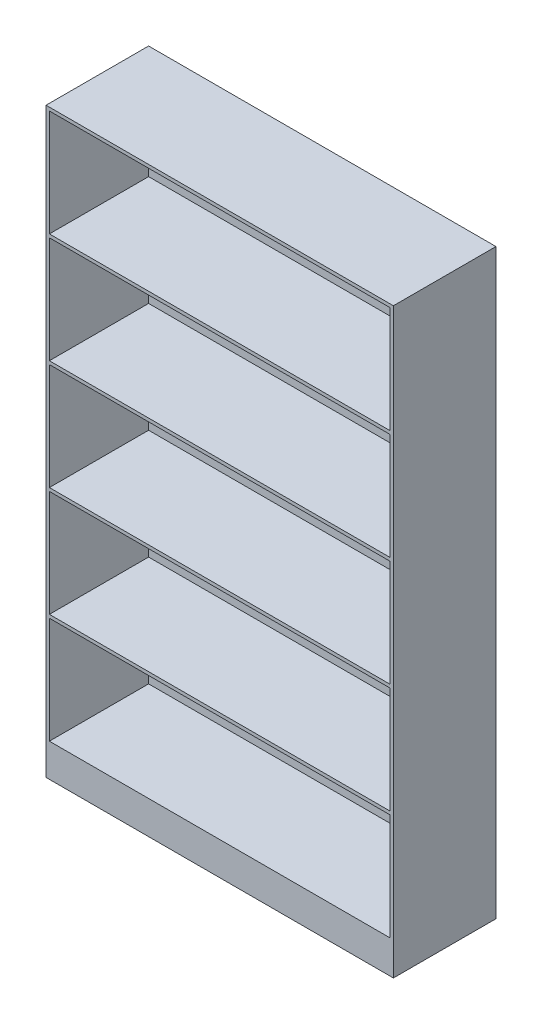
SolidWorks part; units mm, degrees
ref_plane "Alzado" through (0, 0, 0) normal (0, 0, 1) x (1, 0, 0)
ref_plane "Planta" through (0, 0, 0) normal (0, 1, 0) x (1, 0, 0)
ref_plane "Vista lateral" through (0, 0, 0) normal (1, 0, 0) x (0, 0, -1)
sketch "Croquis1" plane through (0, 0, 0) normal (0, 0, 1) x (1, 0, 0)
  line L1 (-525, -880) -> (525, -880)
  line L2 (-525, -880) -> (-525, 880)
  line L3 (-525, 880) -> (525, 880)
  line L4 (525, -880) -> (525, 880)
  line L5 (-525, -880) -> (525, 880) construction
  line L6 (-525, 880) -> (525, -880) construction
  point P0 (0, 0)
  dimension "D1" = 1050
  dimension "D2" = 1760
extrude "Saliente-Extruir1" add sketch "Croquis1" along normal blind 10
sketch "Croquis2" plane through (0, 0, 10) normal (0, 0, 1) x (1, 0, 0)
  line L0 (525, 880) -> (525, -880)
  line L1 (525, -880) -> (-525, -880)
  line L2 (-525, -880) -> (-525, 880)
  line L3 (-525, 880) -> (525, 880)
  line L4 (515, 216) -> (-515, 216)
  line L5 (515, 548) -> (-515, 548)
  line L6 (515, 548) -> (515, 870)
  line L7 (515, 870) -> (-515, 870)
  line L8 (-515, 548) -> (-515, 870)
  line L9 (515, 216) -> (515, 538)
  line L10 (515, 538) -> (-515, 538)
  line L11 (-515, 216) -> (-515, 538)
  line L12 (515, -116) -> (-515, -116)
  line L13 (515, -116) -> (515, 206)
  line L14 (515, 206) -> (-515, 206)
  line L15 (-515, -116) -> (-515, 206)
  line L16 (515, -448) -> (-515, -448)
  line L17 (515, -448) -> (515, -126)
  line L18 (515, -126) -> (-515, -126)
  line L19 (-515, -448) -> (-515, -126)
  line L20 (515, -780) -> (-515, -780)
  line L21 (515, -780) -> (515, -458)
  line L22 (515, -458) -> (-515, -458)
  line L23 (-515, -780) -> (-515, -458)
  dimension "D1" = 5
  dimension "D2" = 10
  dimension "D3" = 10
  dimension "D4" = 10
  dimension "D6" = 10
  dimension "D5" = 100
extrude "Saliente-Extruir2" add sketch "Croquis2" along normal blind 300
